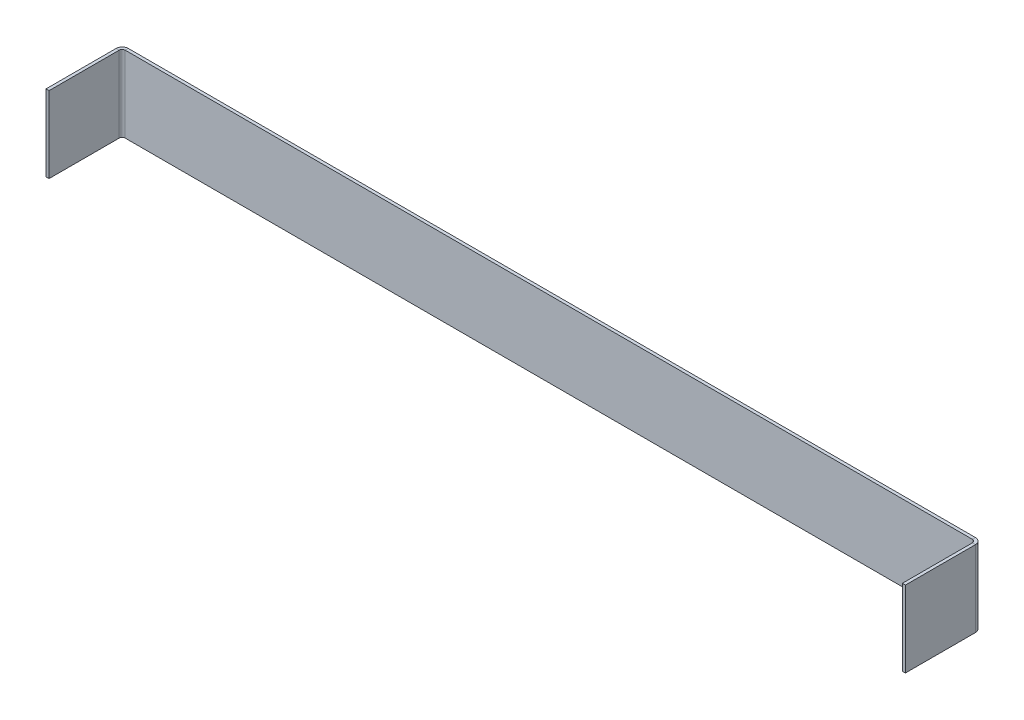
SolidWorks part; units mm, degrees
note: The reader was unsure of these and kept them because the rebuilt part matched: thickness of "Базовая кромка1", "Ребро-кромка1", "Ребро-кромка2", "Листовой металл3", "Листовой металл4", "Листовой металл5"; flange length of "Ребро-кромка1", "Ребро-кромка2".
ref_plane "Спереди" through (0, 0, 0) normal (0, 0, 1) x (1, 0, 0)
ref_plane "Сверху" through (0, 0, 0) normal (0, 1, 0) x (1, 0, 0)
ref_plane "Справа" through (0, 0, 0) normal (1, 0, 0) x (0, 0, -1)
sketch "Эскиз1" plane through (0, 0, 0) normal (0, 0, 1) x (1, 0, 0)
  line L1 (0, 0) -> (564, 0)
  line L2 (0, 0) -> (0, 50)
  line L3 (0, 50) -> (564, 50)
  line L4 (564, 0) -> (564, 50)
base flange "Базовая кромка1" sketch "Эскиз1" thickness 2 reverse thickness direction yes parameters "D1"=2
edge flange "Ребро-кромка1" sketch "Эскиз22" flange angle 90 flange length 50 flange position material inside bend radius 2 thickness 2 relief rectangular parameters "D6"=10
sketch "Эскиз22" plane through (0, 0, 2) normal (-1, 0, 0) x (0, -1, 0)
  line L0 (-50, 0) -> (0, 0) construction
  line L1 (-50, 0) -> (0, 0)
  line L2 (-50, 0) -> (-50, 48)
  line L3 (-50, 48) -> (0, 48)
  line L4 (0, 48) -> (0, 0)
bend "EdgeBend1" bend radius 2 bend angle 90 parameters "D5"=1
edge flange "Ребро-кромка2" sketch "Эскиз25" flange angle 90 flange length 50 flange position material inside bend radius 2 thickness 2 relief rectangular parameters "D6"=10
sketch "Эскиз25" plane through (564, 0, 2) normal (1, 0, 0) x (0, 1, 0)
  line L0 (0, 0) -> (50, 0) construction
  line L1 (0, 0) -> (50, 0)
  line L2 (0, 0) -> (0, 48)
  line L3 (0, 48) -> (50, 48)
  line L4 (50, 48) -> (50, 0)
bend "EdgeBend2" bend radius 2 bend angle 90 parameters "D5"=2
sketch "Сгиб-Линии1" [suppressed] plane through (0, 0, 0) normal (0, 1, 0) x (1, 0, 0)
sketch "Граничная рамка1" [suppressed] plane through (0, 0, 0) normal (0, 1, 0) x (1, 0, 0)
sheet metal parameters "Листовой металл3" thickness 2 parameters "D1"=2
flat pattern "Развертка3" [suppressed]
sketch "Сгиб-Линии3" plane through (0, 0, 0) normal (0, 1, 0) x (1, 0, 0)
sketch3d "Граничная рамка3" [suppressed]
  line L0 (0, 0, 0) -> (560, 0, 0) construction
  line L1 (0, 50, 0) -> (560, 50, 0) construction
  line L2 (0, 0, 0) -> (0, 50, 0) construction
  line L3 (560, 0, 0) -> (560, 50, 0) construction
sheet metal parameters "Листовой металл4" thickness 2 parameters "D1"=2
flat pattern "Развертка3"
sketch "Сгиб-Линии3" plane through (0, 0, 0) normal (0, 0, -1) x (-1, 0, 0)
  line L0 (-1.6438, 0) -> (-1.6438, 50) construction
  line L1 (-1.6438, 0) -> (-1.6438, 50) construction
sketch3d "Граничная рамка3" [suppressed]
  line L0 (46.7124, 0, 0) -> (-560, 0, 0) construction
  line L1 (46.7124, 50, 0) -> (-560, 50, 0) construction
  line L2 (46.7124, 0, 0) -> (46.7124, 50, 0) construction
  line L3 (-560, 0, 0) -> (-560, 50, 0) construction
bend of the flat pattern "Плоское состояние-<EdgeBend1>1"
sheet metal parameters "Листовой металл5" thickness 2 parameters "D1"=2
flat pattern "Развертка3"
sketch "Сгиб-Линии3" plane through (0, 0, 0) normal (0, 0, -1) x (-1, 0, 0)
  line L0 (-1.6438, 0) -> (-1.6438, 50) construction
  line L1 (-1.6438, 0) -> (-1.6438, 50) construction
  line L2 (-558.3562, 50) -> (-558.3562, 0) construction
  line L3 (-558.3562, 50) -> (-558.3562, 0) construction
sketch3d "Граничная рамка3" [suppressed]
  line L0 (46.7124, 0, 0) -> (-606.7124, 0, 0) construction
  line L1 (46.7124, 50, 0) -> (-606.7124, 50, 0) construction
  line L2 (46.7124, 0, 0) -> (46.7124, 50, 0) construction
  line L3 (-606.7124, 0, 0) -> (-606.7124, 50, 0) construction
bend of the flat pattern "Плоское состояние-<EdgeBend1>1"
bend of the flat pattern "Плоское состояние-<EdgeBend2>1"
